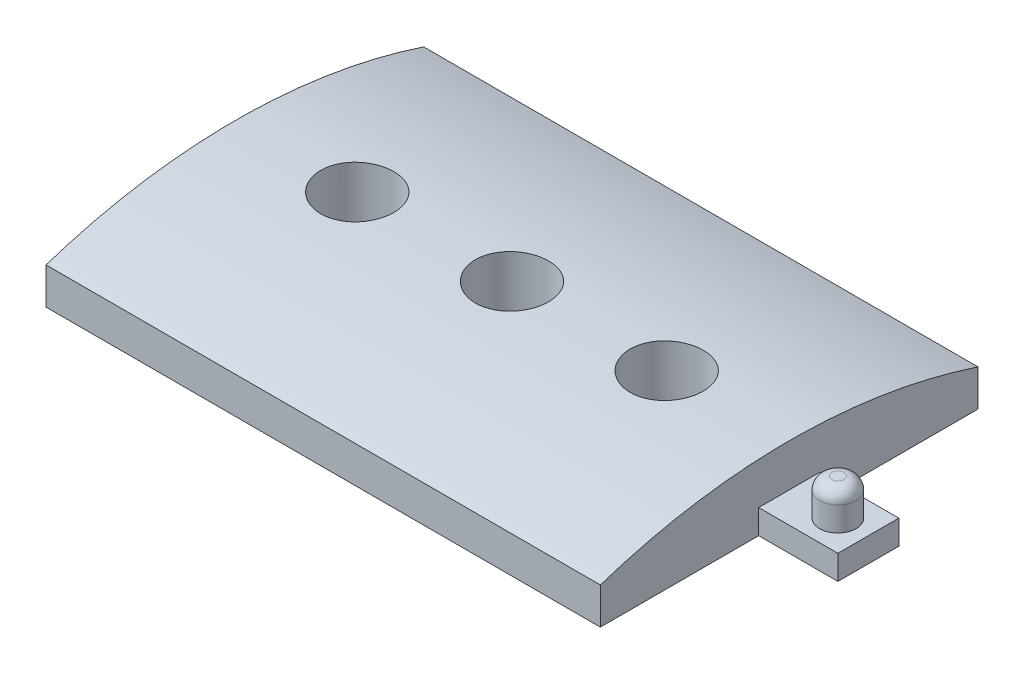
SolidWorks part; units mm, degrees
ref_plane "Front Plane" through (0, 0, 0) normal (0, 0, 1) x (1, 0, 0)
ref_plane "Top Plane" through (0, 0, 0) normal (0, 1, 0) x (1, 0, 0)
ref_plane "Right Plane" through (0, 0, 0) normal (1, 0, 0) x (0, 0, -1)
sketch "Sketch1" plane through (0, 0, 0) normal (0, 1, 0) x (1, 0, 0)
  line L0 (-25.4, 0) -> (0, 0) construction
  line L1 (-45.5, -31) -> (45.5, -31)
  line L2 (-45.5, -31) -> (-45.5, 31)
  line L3 (-45.5, 31) -> (45.5, 31)
  line L4 (45.5, -31) -> (45.5, 31)
  line L5 (-45.5, -31) -> (45.5, 31) construction
  line L6 (-45.5, 31) -> (45.5, -31) construction
  line L7 (0, 0) -> (25.4, 0) construction
  line L9 (38.5, 31) -> (44.5, 31) construction
  circle A0 centre (-25.4, 0) radius 6
  circle A1 centre (0, 0) radius 6
  circle A2 centre (25.4, 0) radius 6
  point P0 (0, 0)
  point P12 (-42.5, 31)
  point P13 (-42.5, 34.2571)
  point P14 (0, 0)
  point P15 (42.1831, 31)
  point P18 (-45.5, 31)
  dimension "D1" = 12
  dimension "D4" = 25.4
extrude "Boss-Extrude1" add sketch "Sketch1" along normal blind 6
ref_plane "Plane1" through (-35, 0, 0) normal (-1, 0, 0) x (0, 0, 1)
sketch "Sketch5" [suppressed] plane through (0, 0, 28.5) normal (0, 0, 1) x (1, 0, 0)
  line L0 (-32, 3.3) -> (-32, -3.3) construction
  line L1 (-36, 5) -> (-28, 5)
  line L2 (-36, 5) -> (-36, 0)
  line L3 (-36, 0) -> (-28, 0)
  line L4 (-28, 5) -> (-28, 0)
  line L5 (-36, 5) -> (-28, 0) construction
  line L6 (-36, 0) -> (-28, 5) construction
  line L7 (-42.5, 0) -> (42.5, 0) construction
  point P0 (-32, 2.5)
  dimension "D1" = 5
  dimension "D2" = 8
sketch "Sketch6" [suppressed] plane through (-32, 0, 0) normal (-1, 0, 0) x (0, 0, 1)
  line L0 (28.5, 2.5) -> (37.5, 2.5)
  line L1 (37.5, 2.5) -> (37.5, -27.5)
  dimension "D1" = 9
  dimension "D2" = 30
sweep "Sweep3" [suppressed] add profiles "Sketch5" path "Sketch6"
mirror "Mirror1" [suppressed] about plane through (0, 0, 0) normal (1, 0, 0)
mirror "Mirror2" [suppressed] about plane through (0, 0, 0) normal (0, 0, 1)
sketch "Sketch16" plane through (0, 0, 0) normal (0, -1, 0) x (1, 0, 0)
  line L0 (45.5, 31) -> (45.5, -31) construction
  line L1 (48.5, 5) -> (45.5, 5)
  line L2 (48.5, 5) -> (48.5, -5)
  line L3 (48.5, -5) -> (45.5, -5)
  line L4 (45.5, 5) -> (45.5, -5)
  line L5 (48.5, 5) -> (45.5, -5) construction
  line L6 (48.5, -5) -> (45.5, 5) construction
  line L8 (58.5, 5) -> (48.5, 5)
  line L9 (58.5, 5) -> (58.5, -5)
  line L10 (58.5, -5) -> (48.5, -5)
  line L11 (48.5, 5) -> (48.5, -5)
  line L12 (58.5, 5) -> (48.5, -5) construction
  line L13 (58.5, -5) -> (48.5, 5) construction
  circle A0 centre (53.5, 0) radius 3
  point P2 (47, 0)
  line M8 (45.5, -31) -> (45.5, 31)
  dimension "D3" = 6
  dimension "D1" = 3
  dimension "D2" = 10
  dimension "D4" = 10
extrude "Boss-Extrude3" add sketch "Sketch16" against normal blind 4 contours L3 L2 L1 M8 | L10 L9 L8 L2 A0 | A0 region at (47, 0, 0) region at (53.5, 0, 4.8586) region at (53.5, 0, 0)
extrude "Boss-Extrude4" add sketch "Sketch16<4>" against normal offset from surface (10 mm away) 6 contours A0 up to face at (52, 4, 0) offset beyond the face yes
sketch "Sketch16<4>" plane through (0, 0, 0) normal (0, -1, 0) x (1, 0, 0) same geometry as "Sketch16"
fillet "Fillet1" radius 2 1 edges at (53.5, 10, -3)
sketch "Sketch17" plane through (-45.5, 0, 0) normal (-1, 0, 0) x (0, 0, 1)
  line L0 (-31, 6) -> (31, 6) construction
  line L1 (-31, 6) -> (31, 6)
  arc A0 (-31, 6) -> (31, 6) centre (0, -87.6) cw
  point P3 (0, 11)
  dimension "D1" = 5
extrude "Boss-Extrude5" add sketch "Sketch17" against normal up to surface (91 mm away) up to face at (45.5, 2.5, 0)
extrude "Cut-Extrude1" cut sketch "Sketch1<2>" along normal through all contours A0 | A1 | A2 region at (-25.4, 0, 0) region at (0, 0, 0) region at (25.4, 0, 0)
sketch "Sketch1<2>" plane through (0, 0, 0) normal (0, 1, 0) x (1, 0, 0) same geometry as "Sketch1"
